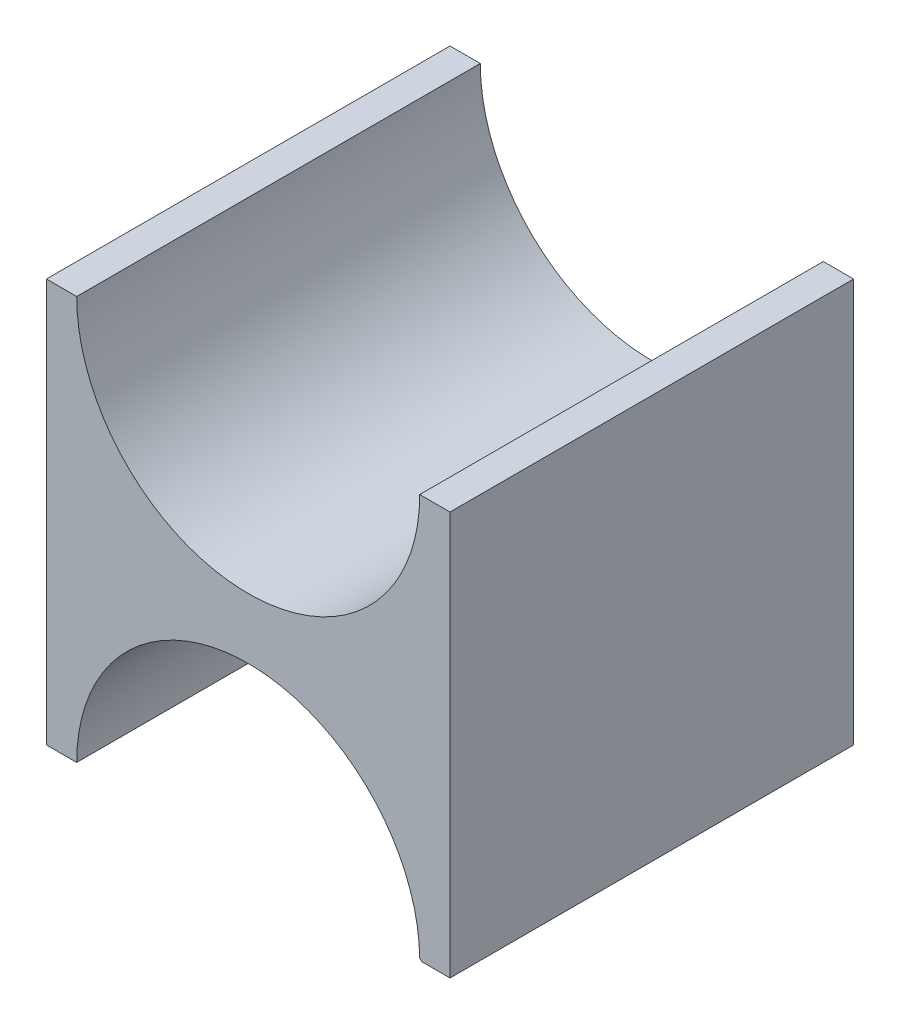
SolidWorks part; units mm, degrees
ref_plane "Front Plane" through (0, 0, 0) normal (0, 0, 1) x (1, 0, 0)
ref_plane "Top Plane" through (0, 0, 0) normal (0, 1, 0) x (1, 0, 0)
ref_plane "Right Plane" through (0, 0, 0) normal (1, 0, 0) x (0, 0, -1)
sketch "Sketch1" plane through (0, 0, 0) normal (0, 0, 1) x (1, 0, 0)
  line L0 (-10, -10) -> (-8.5, -10)
  line L1 (10, -10) -> (8.5, -10)
  line L2 (10, 10) -> (10, -10)
  line L3 (8.5, 10) -> (10, 10)
  line L4 (-10, 10) -> (-10, -10)
  line L7 (-8.5, 10) -> (-10, 10)
  arc A0 (-8.5, -10) -> (8.5, -10) centre (0, -10) cw
  arc A1 (8.5, 10) -> (-8.5, 10) centre (0, 10) cw
  point P0 (0, 0)
extrude "Boss-Extrude1" add sketch "Sketch1" along normal blind 20
sketch "Sketch2" plane through (0, 0, 20) normal (0, 0, 1) x (1, 0, 0)
  line L0 (8.5, -10) -> (8.6046, -10)
  line L1 (8.5, -10) -> (10, -10) construction
  line L2 (8.6046, -10) -> (8.4936, -9.889)
  line L3 (8.4936, -9.889) -> (8.5, -10)
extrude "Cut-Extrude1" cut sketch "Sketch2" against normal through all
